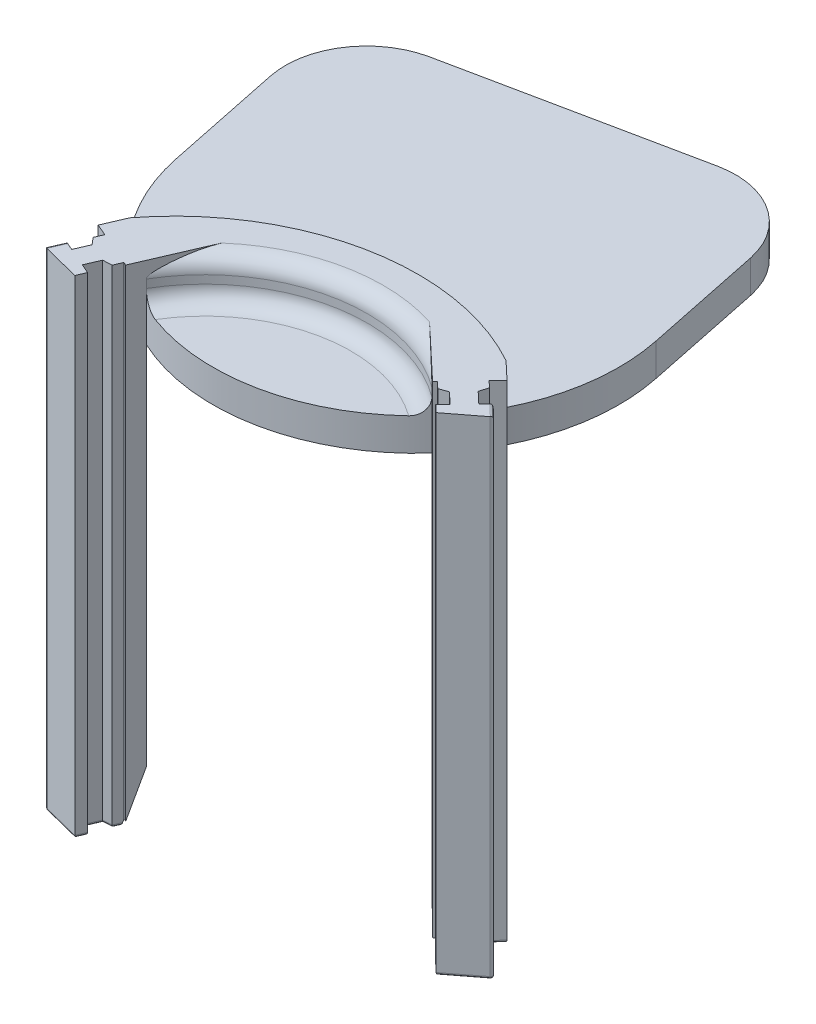
SolidWorks part; units mm, degrees
ref_plane "前视基准面" through (0, 0, 0) normal (0, 0, 1) x (1, 0, 0)
ref_plane "上视基准面" through (0, 0, 0) normal (0, 1, 0) x (1, 0, 0)
ref_plane "右视基准面" through (0, 0, 0) normal (1, 0, 0) x (0, 0, -1)
other "Configuration Table"
sketch "草图1" plane through (0, 0, 0) normal (0, 1, 0) x (1, 0, 0)
  circle A0 centre (0, 0) radius 25
  dimension "D1" = 50
extrude "凸台-拉伸1" add sketch "草图1" along normal blind 4
sketch "草图2" plane through (0, 4, 0) normal (0, 1, 0) x (1, 0, 0)
  line L0 (24.8453, -13.2628) -> (22.4487, -11.0025) construction
  line L1 (23.7738, -14.3989) -> (24.8453, -13.2628) construction
  line L2 (24.5013, -15.085) -> (23.7738, -14.3989) construction
  line L3 (24.179, -16.1555) -> (24.5013, -15.085) construction
  line L4 (25.2702, -17.1847) -> (24.179, -16.1555) construction
  line L5 (25.2702, -17.1847) -> (25.9563, -16.4572) construction
  line L6 (23.2118, -19.3672) -> (22.5257, -20.0947) construction
  line L7 (22.1206, -18.338) -> (23.2118, -19.3672) construction
  line L8 (21.0707, -18.7224) -> (22.1206, -18.338) construction
  line L9 (20.3433, -18.0363) -> (21.0707, -18.7224) construction
  line L10 (20.0516, -18.3456) -> (20.3433, -18.0363) construction
  line L11 (20.0516, -18.3456) -> (18.4671, -16.8512) construction
  line L12 (24.4919, -13.2731) -> (22.3325, -11.2365) construction
  line L13 (23.4204, -14.4092) -> (24.4919, -13.2731) construction
  line L14 (24.2174, -15.1608) -> (23.4204, -14.4092) construction
  line L15 (-17.4055, -25.6275) -> (-18.1973, -27.4641)
  line L16 (-16.2576, -26.1224) -> (-17.4055, -25.6275)
  line L17 (-15.5036, -24.3736) -> (-16.2576, -26.1224)
  line L18 (-16.2239, -23.5185) -> (-15.5036, -24.3736)
  line L19 (-15.7902, -22.5125) -> (-16.2239, -23.5185)
  line L20 (-17.2242, -21.8942) -> (-15.7902, -22.5125)
  line L21 (-16.049, -19.1685) -> (-17.2242, -21.8942)
  line L22 (-11.2675, -24.4625) -> (-10.5021, -22.6871)
  line L23 (-11.6579, -24.2942) -> (-11.2675, -24.4625)
  line L24 (-12.0916, -25.3001) -> (-11.6579, -24.2942)
  line L25 (-13.2079, -25.3634) -> (-12.0916, -25.3001)
  line L26 (-13.9619, -27.1122) -> (-13.2079, -25.3634)
  line L27 (-12.814, -27.6071) -> (-13.9619, -27.1122)
  line L28 (-13.2892, -28.7091) -> (-12.814, -27.6071)
  line L29 (-18.1973, -27.4641) -> (-13.2892, -28.7091)
  line L30 (-17.4055, -25.6275) -> (-18.1973, -27.4641)
  line L31 (-16.2576, -26.1224) -> (-17.4055, -25.6275)
  line L32 (-15.5036, -24.3736) -> (-16.2576, -26.1224)
  line L33 (-16.2239, -23.5185) -> (-15.5036, -24.3736)
  line L34 (-15.7902, -22.5125) -> (-16.2239, -23.5185)
  line L35 (-17.2242, -21.8942) -> (-15.7902, -22.5125)
  line L36 (-16.049, -19.1685) -> (-17.2242, -21.8942)
  line L37 (-11.2675, -24.4625) -> (-10.5021, -22.6871)
  line L38 (-11.6579, -24.2942) -> (-11.2675, -24.4625)
  line L39 (-12.0916, -25.3001) -> (-11.6579, -24.2942)
  line L40 (-13.2079, -25.3634) -> (-12.0916, -25.3001)
  line L41 (-13.9619, -27.1122) -> (-13.2079, -25.3634)
  line L42 (-12.814, -27.6071) -> (-13.9619, -27.1122)
  line L43 (-13.2892, -28.7091) -> (-12.814, -27.6071)
  line L44 (-18.1973, -27.4641) -> (-13.2892, -28.7091)
  line L45 (23.895, -16.2314) -> (24.2174, -15.1608) construction
  line L46 (25.2805, -17.5381) -> (23.895, -16.2314) construction
  line L47 (25.2805, -17.5381) -> (26.1382, -16.6287) construction
  line L48 (26.1382, -16.6287) -> (27.5932, -18.001) construction
  line L49 (23.5806, -21.0895) -> (27.5932, -18.001) construction
  line L50 (22.7076, -20.2662) -> (23.5806, -21.0895) construction
  line L51 (23.5653, -19.3568) -> (22.7076, -20.2662) construction
  line L52 (22.1797, -18.0501) -> (23.5653, -19.3568) construction
  line L53 (21.1299, -18.4346) -> (22.1797, -18.0501) construction
  line L54 (20.3329, -17.6829) -> (21.1299, -18.4346) construction
  line L55 (20.0412, -17.9922) -> (20.3329, -17.6829) construction
  line L56 (20.0412, -17.9922) -> (18.6348, -16.6657) construction
  line L57 (-17.5527, -22.0248) -> (-16.2484, -18.9997) construction
  line L58 (-16.1187, -22.6431) -> (-17.5527, -22.0248) construction
  line L59 (-16.5146, -23.5614) -> (-16.1187, -22.6431) construction
  line L60 (-15.7943, -24.4165) -> (-16.5146, -23.5614) construction
  line L61 (-16.3882, -25.7939) -> (-15.7943, -24.4165) construction
  line L62 (-16.3882, -25.7939) -> (-17.3065, -25.398) construction
  line L63 (-13.6333, -26.9816) -> (-12.7151, -27.3776) construction
  line L64 (-13.0395, -25.6042) -> (-13.6333, -26.9816) construction
  line L65 (-11.9232, -25.541) -> (-13.0395, -25.6042) construction
  line L66 (-11.5273, -24.6227) -> (-11.9232, -25.541) construction
  line L67 (-11.1369, -24.791) -> (-11.5273, -24.6227) construction
  line L68 (24.8453, -13.2628) -> (22.4487, -11.0025)
  line L69 (23.7738, -14.3989) -> (24.8453, -13.2628)
  line L70 (24.5013, -15.085) -> (23.7738, -14.3989)
  line L71 (24.179, -16.1555) -> (24.5013, -15.085)
  line L72 (25.2702, -17.1847) -> (24.179, -16.1555)
  line L73 (25.2702, -17.1847) -> (25.9563, -16.4572)
  line L74 (23.2118, -19.3672) -> (22.5257, -20.0947)
  line L75 (22.1206, -18.338) -> (23.2118, -19.3672)
  line L76 (21.0707, -18.7224) -> (22.1206, -18.338)
  line L77 (20.3433, -18.0363) -> (21.0707, -18.7224)
  line L78 (20.0516, -18.3456) -> (20.3433, -18.0363)
  line L79 (20.0516, -18.3456) -> (18.4671, -16.8512)
  line L80 (24.4919, -13.2731) -> (22.3325, -11.2365)
  line L81 (23.4204, -14.4092) -> (24.4919, -13.2731)
  line L82 (24.2174, -15.1608) -> (23.4204, -14.4092)
  line L83 (23.895, -16.2314) -> (24.2174, -15.1608)
  line L84 (25.2805, -17.5381) -> (23.895, -16.2314)
  line L85 (25.2805, -17.5381) -> (26.1382, -16.6287)
  line L86 (26.1382, -16.6287) -> (27.5932, -18.001)
  line L87 (23.5806, -21.0895) -> (27.5932, -18.001)
  line L88 (22.7076, -20.2662) -> (23.5806, -21.0895)
  line L89 (23.5653, -19.3568) -> (22.7076, -20.2662)
  line L90 (22.1797, -18.0501) -> (23.5653, -19.3568)
  line L91 (21.1299, -18.4346) -> (22.1797, -18.0501)
  line L92 (20.3329, -17.6829) -> (21.1299, -18.4346)
  line L93 (20.0412, -17.9922) -> (20.3329, -17.6829)
  line L94 (20.0412, -17.9922) -> (18.6348, -16.6657)
  line L95 (-17.5527, -22.0248) -> (-16.2484, -18.9997)
  line L96 (-16.1187, -22.6431) -> (-17.5527, -22.0248)
  line L97 (-16.5146, -23.5614) -> (-16.1187, -22.6431)
  line L98 (-15.7943, -24.4165) -> (-16.5146, -23.5614)
  line L99 (-16.3882, -25.7939) -> (-15.7943, -24.4165)
  line L100 (-16.3882, -25.7939) -> (-17.3065, -25.398)
  line L101 (-13.6333, -26.9816) -> (-12.7151, -27.3776)
  line L102 (-13.0395, -25.6042) -> (-13.6333, -26.9816)
  line L103 (-11.9232, -25.541) -> (-13.0395, -25.6042)
  line L104 (-11.5273, -24.6227) -> (-11.9232, -25.541)
  line L105 (-11.1369, -24.791) -> (-11.5273, -24.6227)
  arc A1 (-16.049, -19.1685) -> (-10.5021, -22.6871) centre (0, 0) ccw
  arc A2 (-16.049, -19.1685) -> (-10.5021, -22.6871) centre (0, 0) ccw
  arc A3 (18.6348, -16.6657) -> (22.3325, -11.2365) centre (0, 0) ccw
  circle M17 centre (0, 0) radius 25
  dimension "D1" = 0
extrude "凸台-拉伸2" add sketch "草图2" against normal blind 55 and the other way blind 5 contours L94 L93 L92 L91 L90 L89 L88 L87 L86 L85 L84 L83 L82 L81 L80 M17 | A2 L37 L38 L39 L40 L41 L42 L43 L44 L30 L31 L32 L33 L34 L35 L36
sketch "草图3" plane through (0, 4, 0) normal (0, 1, 0) x (1, 0, 0)
  line L1 (4.0663, -19.6764) -> (13.4386, -65.027) construction
  line L4 (-10.5021, -22.6871) -> (18.6348, -16.6657) construction
  line L5 (4.0663, -19.6764) -> (0, 0) construction
  line L6 (20.0412, -17.9922) -> (18.6348, -16.6657) construction
  arc A5 (-10.5021, -22.6871) -> (18.6348, -16.6657) centre (6.7718, -32.7675) cw
  arc A6 (-16.049, -19.1685) -> (22.3325, -11.2365) centre (7.739, -37.4478) cw
  arc A7 (18.6348, -16.6657) -> (22.3325, -11.2365) centre (0, 0) ccw construction
  arc A8 (-16.049, -19.1685) -> (-10.5021, -22.6871) centre (0, 0) ccw
  arc A9 (-10.5021, -22.6871) -> (18.6348, -16.6657) centre (0, 0) ccw construction
  arc A10 (18.6348, -16.6657) -> (22.3325, -11.2365) centre (0, 0) ccw
  dimension "D1" = 20
  dimension "D2" = 30
extrude "凸台-拉伸3" add sketch "草图3" along normal blind 5
fillet "圆角1" radius 2 2 edges at (2.7241, 4, 13.1814) (2.7241, 9, 13.1814)
chamfer "倒角1" distance 6 angle 20 2 edges at (20.6627, -51, 14.0731) (-13.3916, -51, 21.1108)
chamfer "倒角2" distance 1.5 angle 45 2 edges at (22.3325, -22.5, 11.2365) (-16.049, -22.5, 19.1685)
fillet "圆角3" radius 0.3 28 edges at (-16.5072, -51, 22.2034) (-16.007, -51, 23.0155) (-15.8637, -51, 23.946) (-15.8806, -51, 25.248) (-16.8315, -51, 25.875) (-17.8014, -51, 26.5458) (-15.7432, -51, 28.0866) (-13.0516, -51, 28.1581) (-13.388, -51, 27.3597) (-13.5849, -51, 26.2378) (-12.6497, -51, 25.3318) (-11.9218, -51, 24.9062) (-14.4422, -51, 23.0301) (-17.0861, -51, 21.574) (21.6548, -51, 18.2423) (22.8725, -51, 18.7035) (23.1364, -51, 19.8115) (23.1441, -51, 20.6779) (25.5869, -51, 19.5453) (26.8657, -51, 17.3149) (25.7094, -51, 17.0834) (24.5878, -51, 16.8848) (24.0562, -51, 15.6961) (23.8189, -51, 14.785) (23.9562, -51, 13.8412) (24.2382, -51, 13.0339) (22.388, -51, 15.4187) (20.8178, -51, 18.1402)
fillet "圆角4" radius 0.3 10 edges at (-18.0758, -50.9121, 27.4043) (-17.3596, -50.9121, 25.743) (26.1418, -50.9121, 16.753) (27.4579, -50.9121, 17.9942) (-17.8014, 9, 26.5458) (-18.1973, -20.85, 27.4641) (-17.4055, -20.85, 25.6275) (26.8657, 9, 17.3149) (26.1382, -20.85, 16.6287) (27.5932, -20.85, 18.001)
sketch "草图5" plane through (0, 4, 0) normal (0, 1, 0) x (1, 0, 0)
  line L0 (3.1289, -15.14) -> (0, 0) construction
  line L1 (0, 0) -> (-41.5201, -8.5806) construction
  line L2 (0, 0) -> (-5.0596, 24.4827) construction
  line L3 (-24.4827, -5.0596) -> (-29.5423, 19.423)
  line L4 (-29.5423, 19.423) -> (-5.0596, 24.4827)
  line L5 (24.4827, 5.0596) -> (19.423, 29.5423)
  line L6 (19.423, 29.5423) -> (-5.0596, 24.4827)
  arc A0 (17.2281, -18.1161) -> (-8.6357, -23.4611) centre (6.7718, -32.7675) ccw construction
  arc A1 (22.3325, -11.2365) -> (-16.049, -19.1685) centre (0, 0) ccw construction
  arc A2 (-24.4827, -5.0596) -> (24.4827, 5.0596) centre (0, 0) cw
  point P16 (19.423, 29.5423)
  arc M6 (22.3325, -11.2365) -> (-16.049, -19.1685) centre (0, 0) ccw
extrude "凸台-拉伸4" add sketch "草图5" against normal blind 4 contours L4 L3 M6 | L5 L6 M6
fillet "圆角5" radius 10 2 edges at (19.423, 2, -29.5423) (-29.5423, 2, -19.423)
